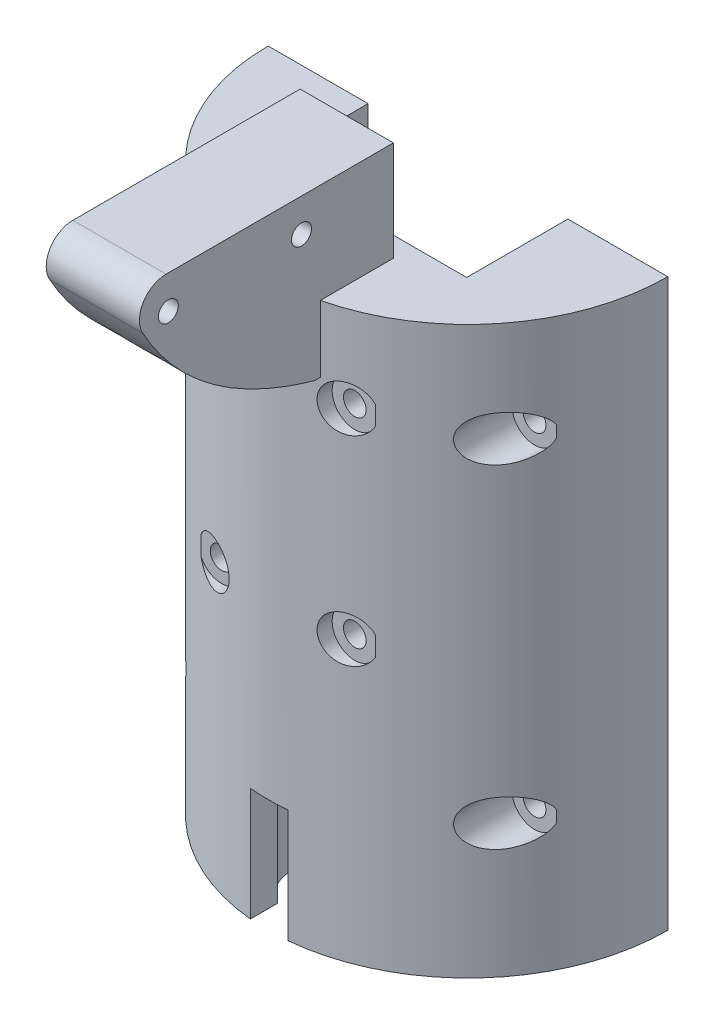
SolidWorks part; units mm, degrees
ref_plane "前视基准面" through (0, 0, 0) normal (0, 0, 1) x (1, 0, 0)
ref_plane "上视基准面" through (0, 0, 0) normal (0, 1, 0) x (1, 0, 0)
ref_plane "右视基准面" through (0, 0, 0) normal (1, 0, 0) x (0, 0, -1)
sketch "草图1" plane through (0, 0, 0) normal (0, 1, 0) x (1, 0, 0)
  line L0 (-30, 0) -> (30, 0)
  line L6 (15, 15.2) -> (-15, 15.2)
  line L7 (15, 15.2) -> (15, -15.2)
  line L8 (15, -15.2) -> (-15, -15.2)
  line L9 (-15, 15.2) -> (-15, -15.2)
  line L10 (15, 15.2) -> (-15, -15.2) construction
  line L11 (15, -15.2) -> (-15, 15.2) construction
  arc A0 (-30, 0) -> (30, 0) centre (0, 0) ccw
  point P0 (0, 0)
  dimension "D3" = 30.4
  dimension "D1" = 30
  dimension "D2" = 60
extrude "凸台-拉伸1" add sketch "草图1" along normal blind 80 contours L0 A0 L8 region at (-22.5, 0, 0.6708)
sketch "草图2" plane through (0, 0, 0) normal (0, 0, 1) x (1, 0, 0)
  line L0 (0, 122.0673) -> (0, -16.729) construction
  line L2 (-30, 0) -> (-15, 0) construction
  circle A0 centre (-10, 37) radius 1.7
  circle A1 centre (-10, 67) radius 1.7
  circle A2 centre (10, 37) radius 1.7
  circle A3 centre (10, 67) radius 1.7
  dimension "D1" = 20
  dimension "D2" = 20
  dimension "D3" = 37
  dimension "D4" = 30
extrude "切除-拉伸1" cut sketch "草图2" along normal blind 100
sketch "草图3" plane through (0, 0, 0) normal (0, 0, -1) x (-1, 0, 0)
  line L0 (-40.9161, 40) -> (57.667, 40) construction
  line L1 (-30, 80) -> (-30, 0) construction
  line L2 (30, 80) -> (30, 0) construction
  line L3 (-30, 0) -> (30, 0) construction
  circle A0 centre (23.5, 65) radius 1.7
  circle A1 centre (-23.5, 65) radius 1.7
  circle A2 centre (23.5, 15) radius 1.7
  circle A3 centre (-23.5, 15) radius 1.7
  dimension "D1" = 50
  dimension "D2" = 50
  dimension "D3" = 6.5
  dimension "D4" = 6.5
  dimension "D5" = 40
extrude "切除-拉伸2" cut sketch "草图3" against normal blind 100
ref_plane "基准面1" through (0, 0, 40) normal (0, 0, -1) x (-1, 0, 0)
sketch "草图4" plane through (0, 0, 40) normal (0, 0, -1) x (-1, 0, 0)
  circle A0 centre (-23.5, 65) radius 3.4
  circle A1 centre (-23.5, 15) radius 3.4
  circle A2 centre (23.5, 65) radius 3.4
  circle A3 centre (23.5, 15) radius 3.4
extrude "切除-拉伸3" cut sketch "草图4" along normal blind 26.5
sketch "草图5" plane through (0, 0, 40) normal (0, 0, -1) x (-1, 0, 0)
  circle A0 centre (-10, 67) radius 3.4
  circle A1 centre (10, 67) radius 3.4
  circle A2 centre (-10, 37) radius 3.4
  circle A3 centre (10, 37) radius 3.4
extrude "切除-拉伸4" cut sketch "草图5" along normal blind 13 contours A2 | A3 | A1 | A0 region at (10, 67, 40) region at (-10, 67, 40) region at (10, 37, 40) region at (-10, 37, 40)
sketch "草图6" plane through (0, 0, 0) normal (0, -1, 0) x (1, 0, 0)
  line L0 (-30, 0) -> (30, 0)
  arc A0 (30, 0) -> (-30, 0) centre (0, 0) ccw
extrude "凸台-拉伸2" add sketch "草图6" along normal blind 3
sketch "草图7" plane through (0, -3, 0) normal (0, -1, 0) x (1, 0, 0)
  line L0 (-30, 0) -> (30, 0) construction
  line L1 (-6, 0) -> (6, 0)
  arc A0 (6, 0) -> (-6, 0) centre (0, 0) ccw
  dimension "D1" = 6
extrude "凸台-拉伸3" add sketch "草图7" along normal blind 9.5
sketch "草图8" plane through (0, 80, 0) normal (0, 1, 0) x (1, 0, 0)
  line L0 (0, 0) -> (0, -36.28) construction
  line L1 (-15, 0) -> (15, 0) construction
  line L2 (-7, -15.2) -> (7, -15.2)
  line L3 (15, -15.2) -> (-15, -15.2) construction
  line L4 (7, -15.2) -> (7, -29.1719)
  line L5 (-7, -15.2) -> (-7, -29.1719)
  arc A0 (-30, 0) -> (30, 0) centre (0, 0) ccw construction
  arc A1 (-7, -29.1719) -> (7, -29.1719) centre (0, 0) ccw
  point P8 (0, -15.2)
  dimension "D1" = 14
ref_plane "基准面2" through (0, 100, 0) normal (0, 1, 0) x (1, 0, 0)
sketch "草图9" plane through (0, 100, 0) normal (0, 1, 0) x (1, 0, 0)
  line L0 (0, 0) -> (0, -36.28) construction
  line L2 (-7, -15.2) -> (7, -15.2)
  line L3 (-7, -15.2) -> (-7, -60.2)
  line L4 (-7, -60.2) -> (7, -60.2)
  line L5 (7, -15.2) -> (7, -60.2)
  dimension "D1" = 14
  dimension "D2" = 45
ref_plane "基准面3" through (0, 70, 0) normal (0, 1, 0) x (1, 0, 0)
sketch "草图10" plane through (0, 70, 0) normal (0, 1, 0) x (1, 0, 0)
  line L0 (-15, 0) -> (15, 0) construction
  line L1 (-7, -29.1719) -> (-7, -15.2)
  line L2 (-7, -15.2) -> (7, -15.2)
  line L3 (7, -15.2) -> (7, -29.1719)
  arc A0 (-7, -29.1719) -> (7, -29.1719) centre (0, 0) ccw
sketch "草图13" plane through (0, 0, 0) normal (1, 0, 0) x (0, 0, -1)
  line L0 (-15.2, 100) -> (-60, 100)
  line L1 (-15.2, 100) -> (-60.2, 100) construction
  line L2 (-15.2, 100) -> (-60.2, 100) construction
  line L3 (-15.2, 100) -> (-15.2, 70)
  line L4 (-15.2, 70) -> (-29.1719, 70) construction
  line L5 (-29.1719, 70) -> (-15.2, 70) construction
  line L6 (-15.2, 70) -> (-30, 70)
  line L7 (-29.1719, 70) -> (-30, 70) construction
  line L8 (-30, 80) -> (-30, -3) construction
  line L9 (0, 80) -> (0, 0) construction
  spline S0 degree 2 poles (-60, 100) (-54.4581, 76.8596) (-30, 70) knots 0 0 0 1 1 1
  dimension "D1" = 15.2
extrude "凸台-拉伸4" add sketch "草图13" along normal mid plane 14
sketch "草图14" plane through (-7, 0, 0) normal (-1, 0, 0) x (0, 0, 1)
  line L0 (0, 80) -> (0, -3) construction
  line L1 (15.2, 100) -> (60, 100) construction
  circle A0 centre (32, 90) radius 1.5
  circle A1 centre (52, 90) radius 1.5
  dimension "D1" = 20
  dimension "D2" = 32
  dimension "D3" = 10
  dimension "D4" = 10
extrude "切除-拉伸6" cut sketch "草图14" against normal blind 14
sketch "草图17" plane through (0, 0, 0) normal (1, 0, 0) x (0, 0, -1)
  line L0 (0, 80) -> (0, -3) construction
  line L1 (-30, -3) -> (0, -3) construction
  circle A0 centre (0, 29) radius 3
  circle A1 centre (0, 49) radius 3
  dimension "D1" = 6
  dimension "D2" = 32
  dimension "D3" = 2
sketch "草图18" plane through (0, 100, 0) normal (0, 1, 0) x (1, 0, 0)
  line L0 (7, -15.2) -> (7, -60) construction
  line L1 (-7, -15.2) -> (7, -15.2)
  line L2 (-7, -15.2) -> (-7, -18.2)
  line L3 (-7, -18.2) -> (7, -18.2)
  line L4 (7, -15.2) -> (7, -18.2)
  dimension "D1" = 3
extrude "切除-拉伸9" cut sketch "草图18" against normal blind 20
sketch "草图19" plane through (0, 0, 0) normal (0, 1, 0) x (1, 0, 0)
  circle A0 centre (0, 0) radius 3
extrude "切除-拉伸10" cut sketch "草图19" against normal blind 3
ref_plane "基准面4" through (0, 26, 0) normal (0, 1, 0) x (1, 0, 0)
fillet "圆角4" radius 1 1 edges at (0, -3, 3)
chamfer "倒角2" distance 2 angle 45 1 edges at (0, 0, 3)
sketch "草图20" plane through (0, -3, 0) normal (0, -1, 0) x (1, 0, 0)
  line L0 (-30, 0) -> (-6, 0) construction
  circle A0 centre (0, 20.5) radius 6
  dimension "D1" = 12
  dimension "D2" = 20.5
extrude "切除-拉伸11" cut sketch "草图20" against normal blind 15
sketch "草图23" plane through (0, 0, 15.2) normal (0, 0, -1) x (-1, 0, 0)
  line L1 (-2.8125, 12) -> (2.8125, 12)
  line L2 (-2.8125, 12) -> (-2.8125, -3.4639)
  line L3 (-2.8125, -3.4639) -> (2.8125, -3.4639)
  line L4 (2.8125, 12) -> (2.8125, -3.4639)
extrude "切除-拉伸14" cut sketch "草图23" against normal blind 30
sketch "草图25" plane through (0, 100, 0) normal (0, 1, 0) x (1, 0, 0)
  line L1 (-7, -18.2) -> (7, -18.2)
  line L2 (-7, -18.2) -> (-7, -60)
  line L3 (-7, -60) -> (7, -60)
  line L4 (7, -18.2) -> (7, -60)
extrude "切除-拉伸16" cut sketch "草图25" against normal blind 5
fillet "圆角6" radius 4 1 edges at (0, 95, 58.5139)
sketch "草图26" plane through (0, -3, 0) normal (0, -1, 0) x (1, 0, 0)
  line L0 (-2.8125, 25.8) -> (-2.8125, 29.8679)
  line L1 (2.8125, 29.8679) -> (2.8125, 25.8)
  line L2 (-30, 0) -> (30, 0)
  arc A2 (-2.8125, 25.8) -> (2.8125, 25.8) centre (0, 20.5) ccw
  arc A3 (6, 0) -> (-6, 0) centre (0, 0) ccw
  arc A4 (30, 0) -> (-30, 0) centre (0, 0) ccw
  line M1 (2.8125, 29.8679) -> (2.8125, 25.8)
  arc M2 (2.8125, 25.8) -> (-2.8125, 25.8) centre (0, 20.5) cw
  line M3 (-2.8125, 25.8) -> (-2.8125, 29.8679)
  arc M4 (-2.8125, 29.8679) -> (-30, 0) centre (0, 0) ccw
  line M5 (-30, 0) -> (-6, 0)
  arc M6 (-6, 0) -> (6, 0) centre (0, 0) cw
  line M7 (6, 0) -> (30, 0)
  arc M8 (30, 0) -> (2.8125, 29.8679) centre (0, 0) ccw
extrude "凸台-拉伸5" add sketch "草图26" along normal blind 2 contours M8 M1 M2 M3 M4 M5 M6 M7 region at (0, -3, 12.2247)
sketch "草图27" plane through (0, -12.5, 0) normal (0, -1, 0) x (1, 0, 0)
  line L0 (-6, 0) -> (6, 0)
  arc A0 (6, 0) -> (-6, 0) centre (0, 0) ccw
extrude "凸台-拉伸6" add sketch "草图27" along normal blind 2
